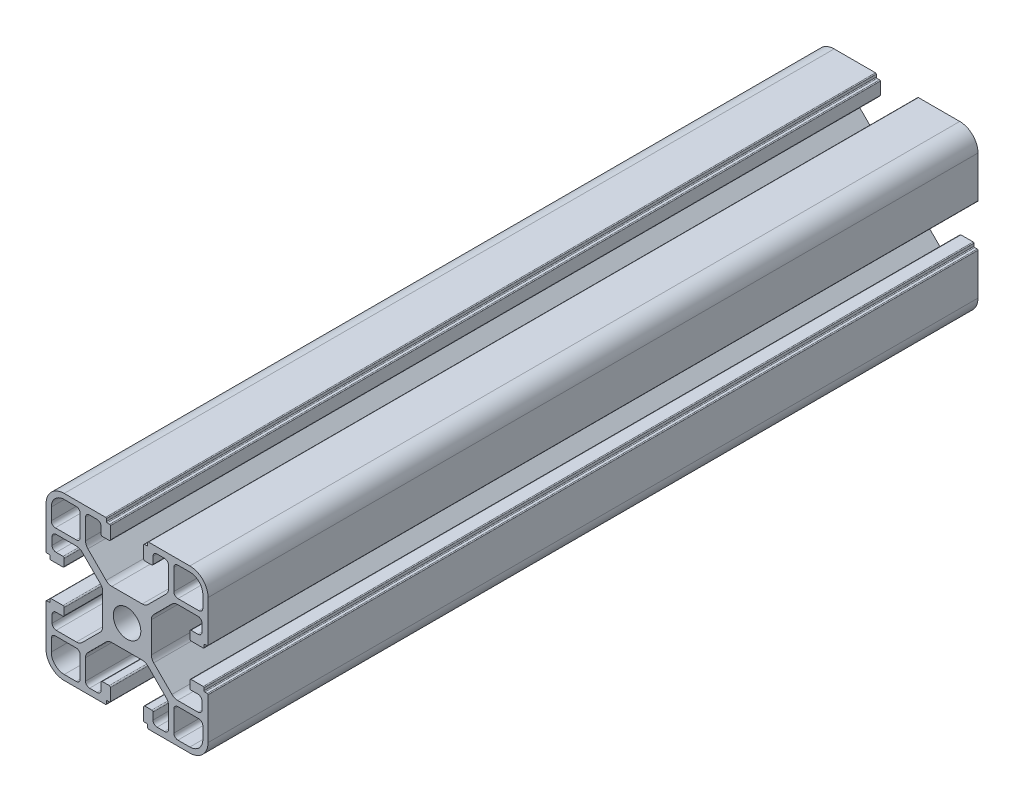
SolidWorks part; units mm, degrees
material "6063-T5"
ref_plane "Front Plane" through (0, 0, 0) normal (0, 0, 1) x (1, 0, 0)
ref_plane "Top Plane" through (0, 0, 0) normal (0, 1, 0) x (1, 0, 0)
ref_plane "Right Plane" through (0, 0, 0) normal (1, 0, 0) x (0, 0, -1)
sketch "Sketch2" plane through (0, 0, 0) normal (0, 0, 1) x (1, 0, 0)
  line L0 (4.5, 0) -> (14.7, 0)
  line L1 (40, 4.5) -> (40, 14.7)
  line L2 (35.5, 40) -> (25.3, 40)
  line L3 (0, 35.5) -> (0, 25.3)
  line L4 (15.9, 1.2) -> (15.9, 4.2)
  line L5 (24.1, 1.2) -> (24.1, 4.2)
  line L6 (38.8, 24.1) -> (35.8, 24.1)
  line L7 (35.5, 24.4) -> (35.5, 26.1)
  line L8 (14, 23.7574) -> (14, 16.2426)
  line L9 (16.2426, 14) -> (23.7574, 14)
  line L10 (26, 16.2426) -> (26, 23.7574)
  line L11 (13.4142, 14.8284) -> (8.9216, 10.3358)
  line L12 (23.7574, 26) -> (16.2426, 26)
  line L13 (4.5, 24.4) -> (4.5, 26.1)
  line L14 (1.2, 24.1) -> (4.2, 24.1)
  line L15 (15.9, 38.8) -> (15.9, 35.8)
  line L16 (14.8284, 26.5858) -> (10.3358, 31.0784)
  line L17 (13.4142, 25.1716) -> (8.9216, 29.6642)
  line L18 (14.8284, 13.4142) -> (10.3358, 8.9216)
  line L19 (25.1716, 13.4142) -> (29.6642, 8.9216)
  line L20 (26.5858, 14.8284) -> (31.0784, 10.3358)
  line L21 (26.5858, 25.1716) -> (31.0784, 29.6642)
  line L22 (25.1716, 26.5858) -> (29.6642, 31.0784)
  line L23 (24.1, 38.8) -> (24.1, 35.8)
  line L24 (14.7, 40) -> (4.5, 40)
  line L25 (25.3, 0) -> (35.5, 0)
  line L26 (38.8, 15.9) -> (35.8, 15.9)
  line L27 (40, 25.3) -> (40, 35.5)
  line L28 (1.2, 15.9) -> (4.2, 15.9)
  line L29 (0, 14.7) -> (0, 4.5)
  line L30 (4.5, 15.6) -> (4.5, 13.9)
  line L31 (35.5, 15.6) -> (35.5, 13.9)
  line L32 (15.6, 35.5) -> (13.9, 35.5)
  line L33 (24.4, 35.5) -> (26.1, 35.5)
  line L34 (15.6, 4.5) -> (13.9, 4.5)
  line L35 (24.4, 4.5) -> (26.1, 4.5)
  line L36 (12.6, 38.5) -> (10.75, 38.5)
  line L37 (1.5, 12.6) -> (1.5, 10.75)
  line L38 (27.4, 1.5) -> (29.25, 1.5)
  line L39 (38.5, 27.4) -> (38.5, 29.25)
  line L40 (38.5, 10.75) -> (38.5, 12.6)
  line L41 (29.25, 38.5) -> (27.4, 38.5)
  line L42 (1.5, 29.25) -> (1.5, 27.4)
  line L43 (10.75, 1.5) -> (12.6, 1.5)
  line L44 (35.8, 26.4) -> (37.5, 26.4)
  line L45 (35.8, 13.6) -> (37.5, 13.6)
  line L46 (4.2, 26.4) -> (2.5, 26.4)
  line L47 (13.6, 35.8) -> (13.6, 37.5)
  line L48 (26.4, 35.8) -> (26.4, 37.5)
  line L49 (4.2, 13.6) -> (2.5, 13.6)
  line L50 (13.6, 4.2) -> (13.6, 2.5)
  line L51 (26.4, 4.2) -> (26.4, 2.5)
  line L52 (9.75, 7.5074) -> (9.75, 2.5)
  line L53 (30.25, 7.5074) -> (30.25, 2.5)
  line L54 (9.75, 37.5) -> (9.75, 32.4926)
  line L55 (30.25, 37.5) -> (30.25, 32.4926)
  line L56 (32.4926, 30.25) -> (37.5, 30.25)
  line L57 (37.5, 9.75) -> (32.4926, 9.75)
  line L58 (2.5, 30.25) -> (7.5074, 30.25)
  line L59 (2.5, 9.75) -> (7.5074, 9.75)
  line L60 (31.55, 37.7) -> (31.55, 32.55)
  line L61 (32.55, 31.55) -> (37.7, 31.55)
  line L62 (1.3, 35.5) -> (1.3, 32.55)
  line L63 (4.5, 38.7) -> (7.45, 38.7)
  line L64 (32.55, 38.7) -> (35.5, 38.7)
  line L65 (38.7, 35.5) -> (38.7, 32.55)
  line L66 (8.45, 37.7) -> (8.45, 32.55)
  line L67 (2.3, 31.55) -> (7.45, 31.55)
  line L68 (1.3, 7.45) -> (1.3, 4.5)
  line L69 (2.3, 8.45) -> (7.45, 8.45)
  line L70 (8.45, 7.45) -> (8.45, 2.3)
  line L71 (4.5, 1.3) -> (7.45, 1.3)
  line L72 (31.55, 7.45) -> (31.55, 2.3)
  line L73 (32.55, 8.45) -> (37.7, 8.45)
  line L74 (38.7, 7.45) -> (38.7, 4.5)
  line L75 (32.55, 1.3) -> (35.5, 1.3)
  line L77 (14.9, 39.8) -> (14.9, 39.2)
  line L78 (15.1, 39) -> (15.7, 39)
  line L79 (25.1, 39.8) -> (25.1, 39.2)
  line L80 (24.9, 39) -> (24.3, 39)
  line L81 (25.1, 0.2) -> (25.1, 0.8)
  line L82 (24.9, 1) -> (24.3, 1)
  line L83 (14.9, 0.2) -> (14.9, 0.8)
  line L84 (15.1, 1) -> (15.7, 1)
  line L85 (0.2, 25.1) -> (0.8, 25.1)
  line L86 (1, 24.9) -> (1, 24.3)
  line L87 (0.2, 14.9) -> (0.8, 14.9)
  line L88 (1, 15.1) -> (1, 15.7)
  line L89 (39.8, 25.1) -> (39.2, 25.1)
  line L90 (39, 24.9) -> (39, 24.3)
  line L91 (39, 15.7) -> (39, 15.1)
  line L92 (39.2, 14.9) -> (39.8, 14.9)
  circle A0 centre (20, 20) radius 3.4
  arc A1 (1.3, 35.5) -> (4.5, 38.7) centre (4.5, 35.5) cw
  arc A2 (1.3, 4.5) -> (4.5, 1.3) centre (4.5, 4.5) ccw
  arc A3 (38.7, 4.5) -> (35.5, 1.3) centre (35.5, 4.5) cw
  arc A4 (35.5, 38.7) -> (38.7, 35.5) centre (35.5, 35.5) cw
  arc A5 (40, 35.5) -> (35.5, 40) centre (35.5, 35.5) ccw
  arc A6 (35.5, 0) -> (40, 4.5) centre (35.5, 4.5) ccw
  arc A7 (4.5, 0) -> (0, 4.5) centre (4.5, 4.5) cw
  arc A8 (4.5, 40) -> (0, 35.5) centre (4.5, 35.5) ccw
  arc A9 (13.4142, 14.8284) -> (14, 16.2426) centre (12, 16.2426) ccw
  arc A10 (7.5074, 9.75) -> (8.9216, 10.3358) centre (7.5074, 11.75) ccw
  arc A11 (9.75, 7.5074) -> (10.3358, 8.9216) centre (11.75, 7.5074) cw
  arc A12 (30.25, 7.5074) -> (29.6642, 8.9216) centre (28.25, 7.5074) ccw
  arc A13 (14.8284, 13.4142) -> (16.2426, 14) centre (16.2426, 12) cw
  arc A14 (25.1716, 13.4142) -> (23.7574, 14) centre (23.7574, 12) ccw
  arc A15 (32.4926, 9.75) -> (31.0784, 10.3358) centre (32.4926, 11.75) cw
  arc A16 (26.5858, 14.8284) -> (26, 16.2426) centre (28, 16.2426) cw
  arc A17 (32.4926, 30.25) -> (31.0784, 29.6642) centre (32.4926, 28.25) ccw
  arc A18 (26.5858, 25.1716) -> (26, 23.7574) centre (28, 23.7574) ccw
  arc A19 (13.4142, 25.1716) -> (14, 23.7574) centre (12, 23.7574) cw
  arc A20 (7.5074, 30.25) -> (8.9216, 29.6642) centre (7.5074, 28.25) cw
  arc A21 (9.75, 32.4926) -> (10.3358, 31.0784) centre (11.75, 32.4926) ccw
  arc A22 (30.25, 32.4926) -> (29.6642, 31.0784) centre (28.25, 32.4926) cw
  arc A23 (25.1716, 26.5858) -> (23.7574, 26) centre (23.7574, 28) cw
  arc A24 (14.8284, 26.5858) -> (16.2426, 26) centre (16.2426, 28) ccw
  arc A25 (37.7, 8.45) -> (38.7, 7.45) centre (37.7, 7.45) cw
  arc A26 (31.55, 2.3) -> (32.55, 1.3) centre (32.55, 2.3) ccw
  arc A27 (31.55, 7.45) -> (32.55, 8.45) centre (32.55, 7.45) cw
  arc A28 (8.45, 2.3) -> (7.45, 1.3) centre (7.45, 2.3) cw
  arc A29 (1.3, 7.45) -> (2.3, 8.45) centre (2.3, 7.45) cw
  arc A30 (7.45, 8.45) -> (8.45, 7.45) centre (7.45, 7.45) cw
  arc A31 (38.7, 32.55) -> (37.7, 31.55) centre (37.7, 32.55) cw
  arc A32 (31.55, 32.55) -> (32.55, 31.55) centre (32.55, 32.55) ccw
  arc A33 (31.55, 37.7) -> (32.55, 38.7) centre (32.55, 37.7) cw
  arc A34 (7.45, 38.7) -> (8.45, 37.7) centre (7.45, 37.7) cw
  arc A35 (8.45, 32.55) -> (7.45, 31.55) centre (7.45, 32.55) cw
  arc A36 (1.3, 32.55) -> (2.3, 31.55) centre (2.3, 32.55) ccw
  arc A37 (30.25, 2.5) -> (29.25, 1.5) centre (29.25, 2.5) cw
  arc A38 (26.4, 2.5) -> (27.4, 1.5) centre (27.4, 2.5) ccw
  arc A39 (13.6, 2.5) -> (12.6, 1.5) centre (12.6, 2.5) cw
  arc A40 (9.75, 2.5) -> (10.75, 1.5) centre (10.75, 2.5) ccw
  arc A41 (26.4, 37.5) -> (27.4, 38.5) centre (27.4, 37.5) cw
  arc A42 (30.25, 37.5) -> (29.25, 38.5) centre (29.25, 37.5) ccw
  arc A43 (37.5, 26.4) -> (38.5, 27.4) centre (37.5, 27.4) ccw
  arc A44 (37.5, 30.25) -> (38.5, 29.25) centre (37.5, 29.25) cw
  arc A45 (37.5, 13.6) -> (38.5, 12.6) centre (37.5, 12.6) cw
  arc A46 (37.5, 9.75) -> (38.5, 10.75) centre (37.5, 10.75) ccw
  arc A47 (2.5, 9.75) -> (1.5, 10.75) centre (2.5, 10.75) cw
  arc A48 (2.5, 13.6) -> (1.5, 12.6) centre (2.5, 12.6) ccw
  arc A49 (2.5, 26.4) -> (1.5, 27.4) centre (2.5, 27.4) cw
  arc A50 (2.5, 30.25) -> (1.5, 29.25) centre (2.5, 29.25) ccw
  arc A51 (9.75, 37.5) -> (10.75, 38.5) centre (10.75, 37.5) cw
  arc A52 (13.6, 37.5) -> (12.6, 38.5) centre (12.6, 37.5) ccw
  arc A53 (26.1, 35.5) -> (26.4, 35.8) centre (26.1, 35.8) ccw
  arc A54 (24.1, 35.8) -> (24.4, 35.5) centre (24.4, 35.8) ccw
  arc A55 (15.9, 35.8) -> (15.6, 35.5) centre (15.6, 35.8) cw
  arc A56 (13.9, 35.5) -> (13.6, 35.8) centre (13.9, 35.8) cw
  arc A57 (13.9, 4.5) -> (13.6, 4.2) centre (13.9, 4.2) ccw
  arc A58 (15.9, 4.2) -> (15.6, 4.5) centre (15.6, 4.2) ccw
  arc A59 (24.1, 4.2) -> (24.4, 4.5) centre (24.4, 4.2) cw
  arc A60 (26.1, 4.5) -> (26.4, 4.2) centre (26.1, 4.2) cw
  arc A61 (35.5, 13.9) -> (35.8, 13.6) centre (35.8, 13.9) ccw
  arc A62 (35.8, 15.9) -> (35.5, 15.6) centre (35.8, 15.6) ccw
  arc A63 (35.8, 24.1) -> (35.5, 24.4) centre (35.8, 24.4) cw
  arc A64 (35.5, 26.1) -> (35.8, 26.4) centre (35.8, 26.1) cw
  arc A65 (4.5, 13.9) -> (4.2, 13.6) centre (4.2, 13.9) cw
  arc A66 (4.2, 15.9) -> (4.5, 15.6) centre (4.2, 15.6) cw
  arc A67 (4.2, 24.1) -> (4.5, 24.4) centre (4.2, 24.4) ccw
  arc A68 (4.5, 26.1) -> (4.2, 26.4) centre (4.2, 26.1) ccw
  arc A69 (25.3, 0) -> (25.1, 0.2) centre (25.3, 0.2) cw
  arc A70 (25.1, 0.8) -> (24.9, 1) centre (24.9, 0.8) ccw
  arc A71 (24.3, 1) -> (24.1, 1.2) centre (24.3, 1.2) cw
  arc A72 (14.7, 0) -> (14.9, 0.2) centre (14.7, 0.2) ccw
  arc A73 (14.9, 0.8) -> (15.1, 1) centre (15.1, 0.8) cw
  arc A74 (15.7, 1) -> (15.9, 1.2) centre (15.7, 1.2) ccw
  arc A75 (39.8, 14.9) -> (40, 14.7) centre (39.8, 14.7) cw
  arc A76 (39, 15.1) -> (39.2, 14.9) centre (39.2, 15.1) ccw
  arc A77 (38.8, 15.9) -> (39, 15.7) centre (38.8, 15.7) cw
  arc A78 (0, 25.3) -> (0.2, 25.1) centre (0.2, 25.3) ccw
  arc A79 (0.8, 25.1) -> (1, 24.9) centre (0.8, 24.9) cw
  arc A80 (1, 24.3) -> (1.2, 24.1) centre (1.2, 24.3) ccw
  arc A81 (0, 14.7) -> (0.2, 14.9) centre (0.2, 14.7) cw
  arc A82 (0.8, 14.9) -> (1, 15.1) centre (0.8, 15.1) ccw
  arc A83 (1, 15.7) -> (1.2, 15.9) centre (1.2, 15.7) cw
  arc A84 (39, 24.3) -> (38.8, 24.1) centre (38.8, 24.3) cw
  arc A85 (39.2, 25.1) -> (39, 24.9) centre (39.2, 24.9) ccw
  arc A86 (40, 25.3) -> (39.8, 25.1) centre (39.8, 25.3) cw
  arc A87 (24.3, 39) -> (24.1, 38.8) centre (24.3, 38.8) ccw
  arc A88 (25.1, 39.2) -> (24.9, 39) centre (24.9, 39.2) cw
  arc A89 (25.3, 40) -> (25.1, 39.8) centre (25.3, 39.8) ccw
  arc A90 (14.9, 39.2) -> (15.1, 39) centre (15.1, 39.2) ccw
  arc A91 (15.7, 39) -> (15.9, 38.8) centre (15.7, 38.8) cw
  arc A92 (14.7, 40) -> (14.9, 39.8) centre (14.7, 39.8) cw
  point P93 (0, 0)
extrude "Boss-Extrude1" add sketch "Sketch2" along normal blind 190
sketch "Sketch3" plane through (0, 0, 190) normal (0, 0, 1) x (1, 0, 0)
  line L76 (25.3, 0) -> (35.5, 0)
  line L77 (40, 4.5) -> (40, 14.7)
  line L78 (39.8, 14.9) -> (39.2, 14.9)
  line L79 (39, 15.1) -> (39, 15.7)
  line L80 (38.8, 15.9) -> (35.8, 15.9)
  line L81 (35.5, 15.6) -> (35.5, 13.9)
  line L82 (35.8, 13.6) -> (37.5, 13.6)
  line L83 (38.5, 12.6) -> (38.5, 10.75)
  line L84 (37.5, 9.75) -> (32.4926, 9.75)
  line L85 (31.0784, 10.3358) -> (26.5858, 14.8284)
  line L86 (26, 16.2426) -> (26, 23.7574)
  line L87 (26.5858, 25.1716) -> (31.0784, 29.6642)
  line L88 (32.4926, 30.25) -> (37.5, 30.25)
  line L89 (38.5, 29.25) -> (38.5, 27.4)
  line L90 (37.5, 26.4) -> (35.8, 26.4)
  line L91 (35.5, 26.1) -> (35.5, 24.4)
  line L92 (35.8, 24.1) -> (38.8, 24.1)
  line L93 (39, 24.3) -> (39, 24.9)
  line L94 (39.2, 25.1) -> (39.8, 25.1)
  line L95 (40, 25.3) -> (40, 35.5)
  line L96 (35.5, 40) -> (25.3, 40)
  line L97 (25.1, 39.8) -> (25.1, 39.2)
  line L98 (24.9, 39) -> (24.3, 39)
  line L99 (24.1, 38.8) -> (24.1, 35.8)
  line L100 (24.4, 35.5) -> (26.1, 35.5)
  line L101 (26.4, 35.8) -> (26.4, 37.5)
  line L102 (27.4, 38.5) -> (29.25, 38.5)
  line L103 (30.25, 37.5) -> (30.25, 32.4926)
  line L104 (29.6642, 31.0784) -> (25.1716, 26.5858)
  line L105 (23.7574, 26) -> (16.2426, 26)
  line L106 (14.8284, 26.5858) -> (10.3358, 31.0784)
  line L107 (9.75, 32.4926) -> (9.75, 37.5)
  line L108 (10.75, 38.5) -> (12.6, 38.5)
  line L109 (13.6, 37.5) -> (13.6, 35.8)
  line L110 (13.9, 35.5) -> (15.6, 35.5)
  line L111 (15.9, 35.8) -> (15.9, 38.8)
  line L112 (15.7, 39) -> (15.1, 39)
  line L113 (14.9, 39.2) -> (14.9, 39.8)
  line L114 (14.7, 40) -> (4.5, 40)
  line L115 (0, 35.5) -> (0, 25.3)
  line L116 (0.2, 25.1) -> (0.8, 25.1)
  line L117 (1, 24.9) -> (1, 24.3)
  line L118 (1.2, 24.1) -> (4.2, 24.1)
  line L119 (4.5, 24.4) -> (4.5, 26.1)
  line L120 (4.2, 26.4) -> (2.5, 26.4)
  line L121 (1.5, 27.4) -> (1.5, 29.25)
  line L122 (2.5, 30.25) -> (7.5074, 30.25)
  line L123 (8.9216, 29.6642) -> (13.4142, 25.1716)
  line L124 (14, 23.7574) -> (14, 16.2426)
  line L125 (13.4142, 14.8284) -> (8.9216, 10.3358)
  line L126 (7.5074, 9.75) -> (2.5, 9.75)
  line L127 (1.5, 10.75) -> (1.5, 12.6)
  line L128 (2.5, 13.6) -> (4.2, 13.6)
  line L129 (4.5, 13.9) -> (4.5, 15.6)
  line L130 (4.2, 15.9) -> (1.2, 15.9)
  line L131 (1, 15.7) -> (1, 15.1)
  line L132 (0.8, 14.9) -> (0.2, 14.9)
  line L133 (0, 14.7) -> (0, 4.5)
  line L134 (4.5, 0) -> (14.7, 0)
  line L135 (14.9, 0.2) -> (14.9, 0.8)
  line L136 (15.1, 1) -> (15.7, 1)
  line L137 (15.9, 1.2) -> (15.9, 4.2)
  line L138 (15.6, 4.5) -> (13.9, 4.5)
  line L139 (13.6, 4.2) -> (13.6, 2.5)
  line L140 (12.6, 1.5) -> (10.75, 1.5)
  line L141 (9.75, 2.5) -> (9.75, 7.5074)
  line L142 (10.3358, 8.9216) -> (14.8284, 13.4142)
  line L143 (16.2426, 14) -> (23.7574, 14)
  line L144 (25.1716, 13.4142) -> (29.6642, 8.9216)
  line L145 (30.25, 7.5074) -> (30.25, 2.5)
  line L146 (29.25, 1.5) -> (27.4, 1.5)
  line L147 (26.4, 2.5) -> (26.4, 4.2)
  line L148 (26.1, 4.5) -> (24.4, 4.5)
  line L149 (24.1, 4.2) -> (24.1, 1.2)
  line L150 (24.3, 1) -> (24.9, 1)
  line L151 (25.1, 0.8) -> (25.1, 0.2)
  line L152 (25.3, 0) -> (35.5, 0)
  line L153 (40, 4.5) -> (40, 14.7)
  line L154 (39.8, 14.9) -> (39.2, 14.9)
  line L155 (39, 15.1) -> (39, 15.7)
  line L156 (38.8, 15.9) -> (35.8, 15.9)
  line L157 (35.5, 15.6) -> (35.5, 13.9)
  line L158 (35.8, 13.6) -> (37.5, 13.6)
  line L159 (38.5, 12.6) -> (38.5, 10.75)
  line L160 (37.5, 9.75) -> (32.4926, 9.75)
  line L161 (31.0784, 10.3358) -> (26.5858, 14.8284)
  line L162 (26, 16.2426) -> (26, 23.7574)
  line L163 (26.5858, 25.1716) -> (31.0784, 29.6642)
  line L164 (32.4926, 30.25) -> (37.5, 30.25)
  line L165 (38.5, 29.25) -> (38.5, 27.4)
  line L166 (37.5, 26.4) -> (35.8, 26.4)
  line L167 (35.5, 26.1) -> (35.5, 24.4)
  line L168 (35.8, 24.1) -> (38.8, 24.1)
  line L169 (39, 24.3) -> (39, 24.9)
  line L170 (39.2, 25.1) -> (39.8, 25.1)
  line L171 (40, 25.3) -> (40, 35.5)
  line L172 (35.5, 40) -> (25.3, 40)
  line L173 (25.1, 39.8) -> (25.1, 39.2)
  line L174 (24.9, 39) -> (24.3, 39)
  line L175 (24.1, 38.8) -> (24.1, 35.8)
  line L176 (24.4, 35.5) -> (26.1, 35.5)
  line L177 (26.4, 35.8) -> (26.4, 37.5)
  line L178 (27.4, 38.5) -> (29.25, 38.5)
  line L179 (30.25, 37.5) -> (30.25, 32.4926)
  line L180 (29.6642, 31.0784) -> (25.1716, 26.5858)
  line L181 (23.7574, 26) -> (16.2426, 26)
  line L182 (14.8284, 26.5858) -> (10.3358, 31.0784)
  line L183 (9.75, 32.4926) -> (9.75, 37.5)
  line L184 (10.75, 38.5) -> (12.6, 38.5)
  line L185 (13.6, 37.5) -> (13.6, 35.8)
  line L186 (13.9, 35.5) -> (15.6, 35.5)
  line L187 (15.9, 35.8) -> (15.9, 38.8)
  line L188 (15.7, 39) -> (15.1, 39)
  line L189 (14.9, 39.2) -> (14.9, 39.8)
  line L190 (14.7, 40) -> (4.5, 40)
  line L191 (0, 35.5) -> (0, 25.3)
  line L192 (0.2, 25.1) -> (0.8, 25.1)
  line L193 (1, 24.9) -> (1, 24.3)
  line L194 (1.2, 24.1) -> (4.2, 24.1)
  line L195 (4.5, 24.4) -> (4.5, 26.1)
  line L196 (4.2, 26.4) -> (2.5, 26.4)
  line L197 (1.5, 27.4) -> (1.5, 29.25)
  line L198 (2.5, 30.25) -> (7.5074, 30.25)
  line L199 (8.9216, 29.6642) -> (13.4142, 25.1716)
  line L200 (14, 23.7574) -> (14, 16.2426)
  line L201 (13.4142, 14.8284) -> (8.9216, 10.3358)
  line L202 (7.5074, 9.75) -> (2.5, 9.75)
  line L203 (1.5, 10.75) -> (1.5, 12.6)
  line L204 (2.5, 13.6) -> (4.2, 13.6)
  line L205 (4.5, 13.9) -> (4.5, 15.6)
  line L206 (4.2, 15.9) -> (1.2, 15.9)
  line L207 (1, 15.7) -> (1, 15.1)
  line L208 (0.8, 14.9) -> (0.2, 14.9)
  line L209 (0, 14.7) -> (0, 4.5)
  line L210 (4.5, 0) -> (14.7, 0)
  line L211 (14.9, 0.2) -> (14.9, 0.8)
  line L212 (15.1, 1) -> (15.7, 1)
  line L213 (15.9, 1.2) -> (15.9, 4.2)
  line L214 (15.6, 4.5) -> (13.9, 4.5)
  line L215 (13.6, 4.2) -> (13.6, 2.5)
  line L216 (12.6, 1.5) -> (10.75, 1.5)
  line L217 (9.75, 2.5) -> (9.75, 7.5074)
  line L218 (10.3358, 8.9216) -> (14.8284, 13.4142)
  line L219 (16.2426, 14) -> (23.7574, 14)
  line L220 (25.1716, 13.4142) -> (29.6642, 8.9216)
  line L221 (30.25, 7.5074) -> (30.25, 2.5)
  line L222 (29.25, 1.5) -> (27.4, 1.5)
  line L223 (26.4, 2.5) -> (26.4, 4.2)
  line L224 (26.1, 4.5) -> (24.4, 4.5)
  line L225 (24.1, 4.2) -> (24.1, 1.2)
  line L226 (24.3, 1) -> (24.9, 1)
  line L227 (25.1, 0.8) -> (25.1, 0.2)
  arc A76 (25.1, 0.2) -> (25.3, 0) centre (25.3, 0.2) ccw
  arc A77 (35.5, 0) -> (40, 4.5) centre (35.5, 4.5) ccw
  arc A78 (40, 14.7) -> (39.8, 14.9) centre (39.8, 14.7) ccw
  arc A79 (39, 15.1) -> (39.2, 14.9) centre (39.2, 15.1) ccw
  arc A80 (39, 15.7) -> (38.8, 15.9) centre (38.8, 15.7) ccw
  arc A81 (35.8, 15.9) -> (35.5, 15.6) centre (35.8, 15.6) ccw
  arc A82 (35.5, 13.9) -> (35.8, 13.6) centre (35.8, 13.9) ccw
  arc A83 (38.5, 12.6) -> (37.5, 13.6) centre (37.5, 12.6) ccw
  arc A84 (37.5, 9.75) -> (38.5, 10.75) centre (37.5, 10.75) ccw
  arc A85 (31.0784, 10.3358) -> (32.4926, 9.75) centre (32.4926, 11.75) ccw
  arc A86 (26, 16.2426) -> (26.5858, 14.8284) centre (28, 16.2426) ccw
  arc A87 (26.5858, 25.1716) -> (26, 23.7574) centre (28, 23.7574) ccw
  arc A88 (32.4926, 30.25) -> (31.0784, 29.6642) centre (32.4926, 28.25) ccw
  arc A89 (38.5, 29.25) -> (37.5, 30.25) centre (37.5, 29.25) ccw
  arc A90 (37.5, 26.4) -> (38.5, 27.4) centre (37.5, 27.4) ccw
  arc A91 (35.8, 26.4) -> (35.5, 26.1) centre (35.8, 26.1) ccw
  arc A92 (35.5, 24.4) -> (35.8, 24.1) centre (35.8, 24.4) ccw
  arc A93 (38.8, 24.1) -> (39, 24.3) centre (38.8, 24.3) ccw
  arc A94 (39.2, 25.1) -> (39, 24.9) centre (39.2, 24.9) ccw
  arc A95 (39.8, 25.1) -> (40, 25.3) centre (39.8, 25.3) ccw
  arc A96 (40, 35.5) -> (35.5, 40) centre (35.5, 35.5) ccw
  arc A97 (25.3, 40) -> (25.1, 39.8) centre (25.3, 39.8) ccw
  arc A98 (24.9, 39) -> (25.1, 39.2) centre (24.9, 39.2) ccw
  arc A99 (24.3, 39) -> (24.1, 38.8) centre (24.3, 38.8) ccw
  arc A100 (24.1, 35.8) -> (24.4, 35.5) centre (24.4, 35.8) ccw
  arc A101 (26.1, 35.5) -> (26.4, 35.8) centre (26.1, 35.8) ccw
  arc A102 (27.4, 38.5) -> (26.4, 37.5) centre (27.4, 37.5) ccw
  arc A103 (30.25, 37.5) -> (29.25, 38.5) centre (29.25, 37.5) ccw
  arc A104 (29.6642, 31.0784) -> (30.25, 32.4926) centre (28.25, 32.4926) ccw
  arc A105 (23.7574, 26) -> (25.1716, 26.5858) centre (23.7574, 28) ccw
  arc A106 (14.8284, 26.5858) -> (16.2426, 26) centre (16.2426, 28) ccw
  arc A107 (9.75, 32.4926) -> (10.3358, 31.0784) centre (11.75, 32.4926) ccw
  arc A108 (10.75, 38.5) -> (9.75, 37.5) centre (10.75, 37.5) ccw
  arc A109 (13.6, 37.5) -> (12.6, 38.5) centre (12.6, 37.5) ccw
  arc A110 (13.6, 35.8) -> (13.9, 35.5) centre (13.9, 35.8) ccw
  arc A111 (15.6, 35.5) -> (15.9, 35.8) centre (15.6, 35.8) ccw
  arc A112 (15.9, 38.8) -> (15.7, 39) centre (15.7, 38.8) ccw
  arc A113 (14.9, 39.2) -> (15.1, 39) centre (15.1, 39.2) ccw
  arc A114 (14.9, 39.8) -> (14.7, 40) centre (14.7, 39.8) ccw
  arc A115 (4.5, 40) -> (0, 35.5) centre (4.5, 35.5) ccw
  arc A116 (0, 25.3) -> (0.2, 25.1) centre (0.2, 25.3) ccw
  arc A117 (1, 24.9) -> (0.8, 25.1) centre (0.8, 24.9) ccw
  arc A118 (1, 24.3) -> (1.2, 24.1) centre (1.2, 24.3) ccw
  arc A119 (4.2, 24.1) -> (4.5, 24.4) centre (4.2, 24.4) ccw
  arc A120 (4.5, 26.1) -> (4.2, 26.4) centre (4.2, 26.1) ccw
  arc A121 (1.5, 27.4) -> (2.5, 26.4) centre (2.5, 27.4) ccw
  arc A122 (2.5, 30.25) -> (1.5, 29.25) centre (2.5, 29.25) ccw
  arc A123 (8.9216, 29.6642) -> (7.5074, 30.25) centre (7.5074, 28.25) ccw
  arc A124 (14, 23.7574) -> (13.4142, 25.1716) centre (12, 23.7574) ccw
  arc A125 (13.4142, 14.8284) -> (14, 16.2426) centre (12, 16.2426) ccw
  arc A126 (7.5074, 9.75) -> (8.9216, 10.3358) centre (7.5074, 11.75) ccw
  arc A127 (1.5, 10.75) -> (2.5, 9.75) centre (2.5, 10.75) ccw
  arc A128 (2.5, 13.6) -> (1.5, 12.6) centre (2.5, 12.6) ccw
  arc A129 (4.2, 13.6) -> (4.5, 13.9) centre (4.2, 13.9) ccw
  arc A130 (4.5, 15.6) -> (4.2, 15.9) centre (4.2, 15.6) ccw
  arc A131 (1.2, 15.9) -> (1, 15.7) centre (1.2, 15.7) ccw
  arc A132 (0.8, 14.9) -> (1, 15.1) centre (0.8, 15.1) ccw
  arc A133 (0.2, 14.9) -> (0, 14.7) centre (0.2, 14.7) ccw
  arc A134 (0, 4.5) -> (4.5, 0) centre (4.5, 4.5) ccw
  arc A135 (14.7, 0) -> (14.9, 0.2) centre (14.7, 0.2) ccw
  arc A136 (15.1, 1) -> (14.9, 0.8) centre (15.1, 0.8) ccw
  arc A137 (15.7, 1) -> (15.9, 1.2) centre (15.7, 1.2) ccw
  arc A138 (15.9, 4.2) -> (15.6, 4.5) centre (15.6, 4.2) ccw
  arc A139 (13.9, 4.5) -> (13.6, 4.2) centre (13.9, 4.2) ccw
  arc A140 (12.6, 1.5) -> (13.6, 2.5) centre (12.6, 2.5) ccw
  arc A141 (9.75, 2.5) -> (10.75, 1.5) centre (10.75, 2.5) ccw
  arc A142 (10.3358, 8.9216) -> (9.75, 7.5074) centre (11.75, 7.5074) ccw
  arc A143 (16.2426, 14) -> (14.8284, 13.4142) centre (16.2426, 12) ccw
  arc A144 (25.1716, 13.4142) -> (23.7574, 14) centre (23.7574, 12) ccw
  arc A145 (30.25, 7.5074) -> (29.6642, 8.9216) centre (28.25, 7.5074) ccw
  arc A146 (29.25, 1.5) -> (30.25, 2.5) centre (29.25, 2.5) ccw
  arc A147 (26.4, 2.5) -> (27.4, 1.5) centre (27.4, 2.5) ccw
  arc A148 (26.4, 4.2) -> (26.1, 4.5) centre (26.1, 4.2) ccw
  arc A149 (24.4, 4.5) -> (24.1, 4.2) centre (24.4, 4.2) ccw
  arc A150 (24.1, 1.2) -> (24.3, 1) centre (24.3, 1.2) ccw
  arc A151 (25.1, 0.8) -> (24.9, 1) centre (24.9, 0.8) ccw
  arc A152 (25.1, 0.2) -> (25.3, 0) centre (25.3, 0.2) ccw
  arc A153 (35.5, 0) -> (40, 4.5) centre (35.5, 4.5) ccw
  arc A154 (40, 14.7) -> (39.8, 14.9) centre (39.8, 14.7) ccw
  arc A155 (39, 15.1) -> (39.2, 14.9) centre (39.2, 15.1) ccw
  arc A156 (39, 15.7) -> (38.8, 15.9) centre (38.8, 15.7) ccw
  arc A157 (35.8, 15.9) -> (35.5, 15.6) centre (35.8, 15.6) ccw
  arc A158 (35.5, 13.9) -> (35.8, 13.6) centre (35.8, 13.9) ccw
  arc A159 (38.5, 12.6) -> (37.5, 13.6) centre (37.5, 12.6) ccw
  arc A160 (37.5, 9.75) -> (38.5, 10.75) centre (37.5, 10.75) ccw
  arc A161 (31.0784, 10.3358) -> (32.4926, 9.75) centre (32.4926, 11.75) ccw
  arc A162 (26, 16.2426) -> (26.5858, 14.8284) centre (28, 16.2426) ccw
  arc A163 (26.5858, 25.1716) -> (26, 23.7574) centre (28, 23.7574) ccw
  arc A164 (32.4926, 30.25) -> (31.0784, 29.6642) centre (32.4926, 28.25) ccw
  arc A165 (38.5, 29.25) -> (37.5, 30.25) centre (37.5, 29.25) ccw
  arc A166 (37.5, 26.4) -> (38.5, 27.4) centre (37.5, 27.4) ccw
  arc A167 (35.8, 26.4) -> (35.5, 26.1) centre (35.8, 26.1) ccw
  arc A168 (35.5, 24.4) -> (35.8, 24.1) centre (35.8, 24.4) ccw
  arc A169 (38.8, 24.1) -> (39, 24.3) centre (38.8, 24.3) ccw
  arc A170 (39.2, 25.1) -> (39, 24.9) centre (39.2, 24.9) ccw
  arc A171 (39.8, 25.1) -> (40, 25.3) centre (39.8, 25.3) ccw
  arc A172 (40, 35.5) -> (35.5, 40) centre (35.5, 35.5) ccw
  arc A173 (25.3, 40) -> (25.1, 39.8) centre (25.3, 39.8) ccw
  arc A174 (24.9, 39) -> (25.1, 39.2) centre (24.9, 39.2) ccw
  arc A175 (24.3, 39) -> (24.1, 38.8) centre (24.3, 38.8) ccw
  arc A176 (24.1, 35.8) -> (24.4, 35.5) centre (24.4, 35.8) ccw
  arc A177 (26.1, 35.5) -> (26.4, 35.8) centre (26.1, 35.8) ccw
  arc A178 (27.4, 38.5) -> (26.4, 37.5) centre (27.4, 37.5) ccw
  arc A179 (30.25, 37.5) -> (29.25, 38.5) centre (29.25, 37.5) ccw
  arc A180 (29.6642, 31.0784) -> (30.25, 32.4926) centre (28.25, 32.4926) ccw
  arc A181 (23.7574, 26) -> (25.1716, 26.5858) centre (23.7574, 28) ccw
  arc A182 (14.8284, 26.5858) -> (16.2426, 26) centre (16.2426, 28) ccw
  arc A183 (9.75, 32.4926) -> (10.3358, 31.0784) centre (11.75, 32.4926) ccw
  arc A184 (10.75, 38.5) -> (9.75, 37.5) centre (10.75, 37.5) ccw
  arc A185 (13.6, 37.5) -> (12.6, 38.5) centre (12.6, 37.5) ccw
  arc A186 (13.6, 35.8) -> (13.9, 35.5) centre (13.9, 35.8) ccw
  arc A187 (15.6, 35.5) -> (15.9, 35.8) centre (15.6, 35.8) ccw
  arc A188 (15.9, 38.8) -> (15.7, 39) centre (15.7, 38.8) ccw
  arc A189 (14.9, 39.2) -> (15.1, 39) centre (15.1, 39.2) ccw
  arc A190 (14.9, 39.8) -> (14.7, 40) centre (14.7, 39.8) ccw
  arc A191 (4.5, 40) -> (0, 35.5) centre (4.5, 35.5) ccw
  arc A192 (0, 25.3) -> (0.2, 25.1) centre (0.2, 25.3) ccw
  arc A193 (1, 24.9) -> (0.8, 25.1) centre (0.8, 24.9) ccw
  arc A194 (1, 24.3) -> (1.2, 24.1) centre (1.2, 24.3) ccw
  arc A195 (4.2, 24.1) -> (4.5, 24.4) centre (4.2, 24.4) ccw
  arc A196 (4.5, 26.1) -> (4.2, 26.4) centre (4.2, 26.1) ccw
  arc A197 (1.5, 27.4) -> (2.5, 26.4) centre (2.5, 27.4) ccw
  arc A198 (2.5, 30.25) -> (1.5, 29.25) centre (2.5, 29.25) ccw
  arc A199 (8.9216, 29.6642) -> (7.5074, 30.25) centre (7.5074, 28.25) ccw
  arc A200 (14, 23.7574) -> (13.4142, 25.1716) centre (12, 23.7574) ccw
  arc A201 (13.4142, 14.8284) -> (14, 16.2426) centre (12, 16.2426) ccw
  arc A202 (7.5074, 9.75) -> (8.9216, 10.3358) centre (7.5074, 11.75) ccw
  arc A203 (1.5, 10.75) -> (2.5, 9.75) centre (2.5, 10.75) ccw
  arc A204 (2.5, 13.6) -> (1.5, 12.6) centre (2.5, 12.6) ccw
  arc A205 (4.2, 13.6) -> (4.5, 13.9) centre (4.2, 13.9) ccw
  arc A206 (4.5, 15.6) -> (4.2, 15.9) centre (4.2, 15.6) ccw
  arc A207 (1.2, 15.9) -> (1, 15.7) centre (1.2, 15.7) ccw
  arc A208 (0.8, 14.9) -> (1, 15.1) centre (0.8, 15.1) ccw
  arc A209 (0.2, 14.9) -> (0, 14.7) centre (0.2, 14.7) ccw
  arc A210 (0, 4.5) -> (4.5, 0) centre (4.5, 4.5) ccw
  arc A211 (14.7, 0) -> (14.9, 0.2) centre (14.7, 0.2) ccw
  arc A212 (15.1, 1) -> (14.9, 0.8) centre (15.1, 0.8) ccw
  arc A213 (15.7, 1) -> (15.9, 1.2) centre (15.7, 1.2) ccw
  arc A214 (15.9, 4.2) -> (15.6, 4.5) centre (15.6, 4.2) ccw
  arc A215 (13.9, 4.5) -> (13.6, 4.2) centre (13.9, 4.2) ccw
  arc A216 (12.6, 1.5) -> (13.6, 2.5) centre (12.6, 2.5) ccw
  arc A217 (9.75, 2.5) -> (10.75, 1.5) centre (10.75, 2.5) ccw
  arc A218 (10.3358, 8.9216) -> (9.75, 7.5074) centre (11.75, 7.5074) ccw
  arc A219 (16.2426, 14) -> (14.8284, 13.4142) centre (16.2426, 12) ccw
  arc A220 (25.1716, 13.4142) -> (23.7574, 14) centre (23.7574, 12) ccw
  arc A221 (30.25, 7.5074) -> (29.6642, 8.9216) centre (28.25, 7.5074) ccw
  arc A222 (29.25, 1.5) -> (30.25, 2.5) centre (29.25, 2.5) ccw
  arc A223 (26.4, 2.5) -> (27.4, 1.5) centre (27.4, 2.5) ccw
  arc A224 (26.4, 4.2) -> (26.1, 4.5) centre (26.1, 4.2) ccw
  arc A225 (24.4, 4.5) -> (24.1, 4.2) centre (24.4, 4.2) ccw
  arc A226 (24.1, 1.2) -> (24.3, 1) centre (24.3, 1.2) ccw
  arc A227 (25.1, 0.8) -> (24.9, 1) centre (24.9, 0.8) ccw
  dimension "D1" = 0
sketch "Sketch4" plane through (0, 0, 0) normal (-1, 0, 0) x (0, 0, 1)
  line L0 (15, 20) -> (68, 20) construction
  line L2 (0, 23.7574) -> (0, 16.2426) construction
  circle A0 centre (15, 20) radius 2.5
  circle A1 centre (68, 20) radius 2.5
  dimension "D1" = 5
  dimension "D2" = 53
  dimension "D3" = 15
extrude "Cut-Extrude1" cut sketch "Sketch4" against normal through all contours A1 | A0 region at (0, 20, 68)
